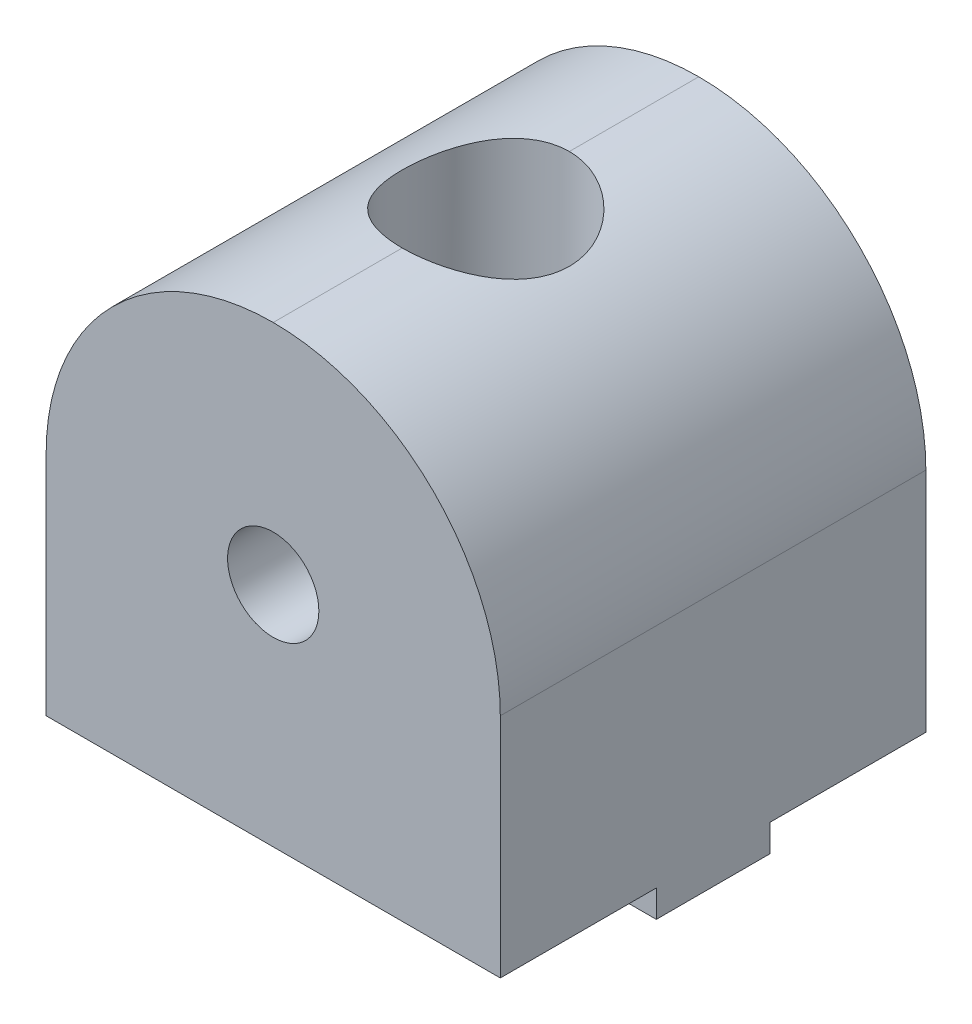
SolidWorks part; units mm, degrees
ref_plane "Front"
ref_plane "Top" through (0, 0, 0) normal (0, 1, 0) x (1, 0, 0)
ref_plane "Right" through (0, 0, 0) normal (1, 0, 0) x (0, 0, -1)
sketch "Sketch1" plane through (0, 0, 0) normal (0, 0, 1) x (1, 0, 0)
  line L1 (-12.7, 0) -> (12.7, 0)
  line L2 (12.7, 0) -> (12.7, 12.7)
  line L3 (-12.7, 0) -> (-12.7, 25.4)
  line L4 (0, 25.4) -> (-12.7, 25.4)
  arc A0 (12.7, 12.7) -> (0, 25.4) centre (0, 12.7) ccw
  point P6 (0, 0)
  point P7 (0, 0)
  dimension "D3" = 12.7
  dimension "D1" = 25.4
  dimension "D2" = 25.4
extrude "Extrude1" add sketch "Sketch1" against normal blind 23.7998
hole_wizard "1/4-20 Tapped Hole2" positions "Sketch6" profile "Sketch5" tap size "1/4-20" standard "Ansi Inch"
sketch "Sketch6" plane through (0, 0, 0) normal (0, 0, 1) x (1, 0, 0)
  line L0 (-12.7, 25.4) -> (-12.7, 0) construction
  line L1 (-12.7, 0) -> (12.7, 0) construction
  point P0 (0, 12.7)
  dimension "D1" = 12.7
  dimension "D2" = 12.7
sketch "Sketch5" plane through (0, 12.7, 0) normal (1, 0, 0) x (0, -1, 0)
  line L0 (0, 0) -> (0, 23.7998)
  line L1 (0, 23.7998) -> (2.5527, 23.7998)
  line L2 (2.5527, 23.7998) -> (2.5527, 0)
  line L5 (2.5527, 0) -> (0, 0)
  line L11 (0, -6.35) -> (0, 107.95) construction
  dimension "Thru Tap Drill Dia." = 5.1054
  dimension "Thru Tap Drill Depth" = 23.7998
cosmetic thread "Cosmetic Thread2" parameters "D2"=6.35
hole_wizard "CBORE for 1/4 Socket Head Cap Screw1" positions "Sketch11" profile "Sketch10" counterbore size "1/4" standard "Ansi Inch"
sketch "Sketch11" plane through (0, 25.4, 0) normal (0, 1, 0) x (-1, 0, 0)
  line L0 (12.7, -23.7998) -> (12.7, 0) construction
  line L1 (0, 0) -> (12.7, 0) construction
  point P0 (0, -11.8872)
  dimension "D1" = 12.7
  dimension "D2" = 11.8872
sketch "Sketch10" plane through (0, 25.4, -11.8872) normal (1, 0, 0) x (0, 0, 1)
  line L0 (0, 0) -> (0, 25.4)
  line L1 (0, 25.4) -> (3.2639, 25.4)
  line L3 (3.2639, 25.4) -> (3.2639, 7.9248)
  line L4 (3.2639, 7.9248) -> (4.6736, 7.9248)
  line L5 (4.6736, 7.9248) -> (4.6736, 0)
  line L7 (4.6736, 0) -> (0, 0)
  line L11 (0, -6.35) -> (0, 107.95) construction
  dimension "Thru Hole Dia." = 6.5278
  dimension "Thru Hole Depth" = 25.4
  dimension "C'Bore Dia." = 9.3472
  dimension "C'Bore Depth" = 7.9248
sketch "Sketch12" plane through (8.7992, 0, -6.8353) normal (0, -1, 0) x (1, 0, 0)
  line L0 (-8.7992, 6.8353) -> (-8.7992, -16.9645) construction
  line L1 (3.9008, -1.8896) -> (-2.4492, -1.8896)
  line L2 (-21.4992, -16.9645) -> (3.9008, -16.9645) construction
  line L3 (-2.4492, -1.8896) -> (-2.4492, -8.2396)
  line L4 (-21.4992, -16.9645) -> (-21.4992, 6.8353) construction
  line L5 (-2.4492, -8.2396) -> (3.9008, -8.2396)
  line L6 (3.9008, -16.9645) -> (3.9008, 6.8353) construction
  line L7 (3.9008, -8.2396) -> (3.9008, -1.8896)
  line L8 (-21.4992, -8.2396) -> (-21.4992, -1.8896)
  line L10 (-21.4992, -5.0646) -> (3.9008, -5.0646) construction
  line L11 (-15.1492, -8.2396) -> (-21.4992, -8.2396)
  line L12 (-15.1492, -1.8896) -> (-15.1492, -8.2396)
  line L13 (-21.4992, -1.8896) -> (-15.1492, -1.8896)
  point P18 (3.9008, -5.0646)
  dimension "D1" = 6.35
  dimension "D2" = 6.35
extrude "Extrude2" add sketch "Sketch12" along normal blind 1.524
fillet "Fillet1" radius 12.7
